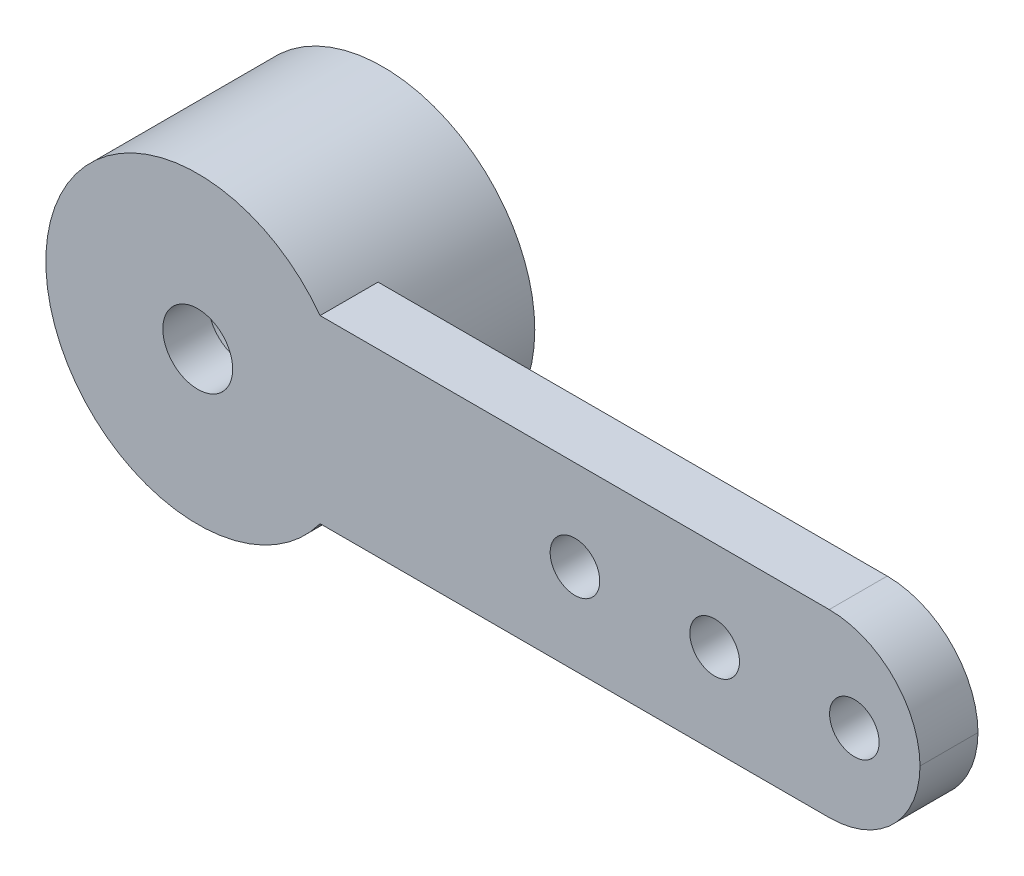
SolidWorks part; units mm, degrees
ref_plane "Front Plane" through (0, 0, 0) normal (0, 0, 1) x (1, 0, 0)
ref_plane "Top Plane" through (0, 0, 0) normal (0, 1, 0) x (1, 0, 0)
ref_plane "Right Plane" through (0, 0, 0) normal (1, 0, 0) x (0, 0, -1)
sketch "Sketch1" plane through (0, 0, 0) normal (0, 0, 1) x (1, 0, 0)
  circle A0 centre (0, 0) radius 2.7622
  dimension "D1" = 5.5245
extrude "Boss-Extrude1" add sketch "Sketch1" along normal blind 3.3655
sketch "Sketch2" plane through (0, 0, 3.3655) normal (0, 0, 1) x (1, 0, 0)
  line L1 (0, 1.6383) -> (13.1318, 1.6383)
  line L2 (0, 1.6383) -> (0, -1.6383)
  line L3 (0, -1.6383) -> (13.1318, -1.6383)
  line L4 (13.1318, 1.6383) -> (13.1318, -1.6383)
  point P4 (0, 0)
  point P5 (0, 0)
  dimension "D1" = 13.1318
  dimension "D2" = 3.2766
extrude "Boss-Extrude2" add sketch "Sketch2" against normal blind 1.0541
fillet "Fillet1" radius 1.651 2 edges at (13.1318, -1.6383, 2.8385) (13.1318, 1.6383, 2.8385)
sketch "Sketch3" plane through (0, 0, 3.3655) normal (0, 0, 1) x (1, 0, 0)
  circle A0 centre (0, 0) radius 0.635
  dimension "D1" = 1.27
extrude "Cut-Extrude1" cut sketch "Sketch3" against normal up to surface (3.3655 mm away) up to face at (2.7622, 0, 0)
sketch "Sketch4" plane through (0, 0, 0) normal (0, 0, -1) x (-1, 0, 0)
  circle A0 centre (0, 0) radius 1.4922
  circle A1 centre (0, 0) radius 2.7622 construction
  dimension "D1" = 1.27
extrude "Cut-Extrude2" cut sketch "Sketch4" against normal offset from surface (2.54 mm away) 2.54 up to face at (0.635, 0, 0)
sketch "Sketch5" plane through (0, 0, 3.3655) normal (0, 0, 1) x (1, 0, 0)
  line L0 (0, 0) -> (13.1318, 0) construction
  circle A0 centre (6.858, 0) radius 0.4508
  circle A1 centre (0, 0) radius 0.635 construction
  circle A2 centre (9.398, 0) radius 0.4508
  circle A3 centre (11.938, 0) radius 0.4508
  dimension "D2" = 0.9017
  dimension "D1" = 6.858
  dimension "D3" = 2.54
  dimension "D4" = 2.54
extrude "Cut-Extrude3" cut sketch "Sketch5" against normal through all
